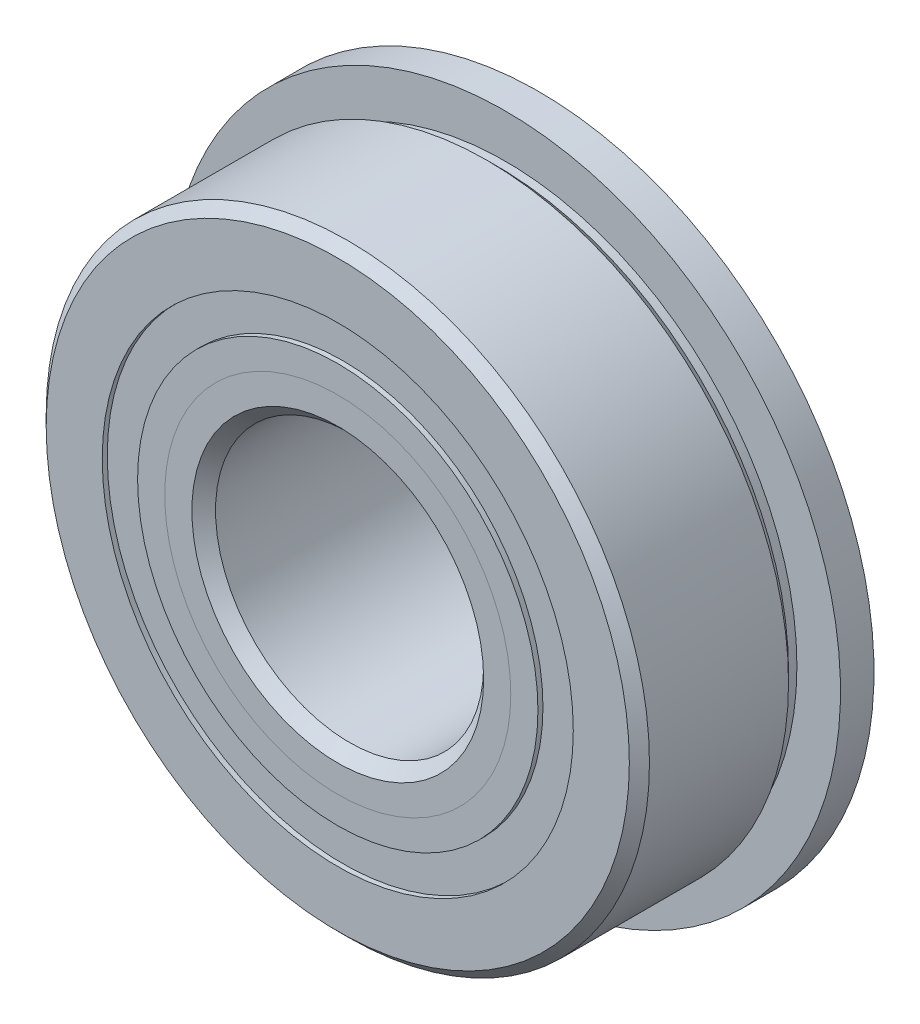
SolidWorks part; units mm, degrees
ref_plane "Front Plane" through (0, 0, 0) normal (0, 0, 1) x (1, 0, 0)
ref_plane "Top Plane" through (0, 0, 0) normal (0, 1, 0) x (1, 0, 0)
ref_plane "Right Plane" through (0, 0, 0) normal (1, 0, 0) x (0, 0, -1)
sketch "Sketch1" plane through (0, 0, 0) normal (1, 0, 0) x (0, 0, -1)
  line L0 (-4.7625, 0) -> (4.7625, 0) construction
  line L1 (0, 14.2875) -> (0, -14.2875) construction
  line L2 (4.2863, 14.2875) -> (-4.2863, 14.2875)
  line L3 (-4.2863, 14.2875) -> (-4.7625, 13.8113)
  line L4 (-4.7625, 13.8113) -> (-4.7625, 11.1561)
  line L5 (-4.7625, 11.1561) -> (-2.7214, 11.1561)
  line L6 (4.7625, 11.1561) -> (2.7214, 11.1561)
  line L7 (4.7625, 13.8113) -> (4.7625, 11.1561)
  line L8 (4.2863, 14.2875) -> (4.7625, 13.8113)
  line L9 (0, 14.2875) -> (0, 10.3187) construction
  line L10 (0, 10.3187) -> (0, 6.35) construction
  line L11 (4.7625, 0) -> (6.35, 0) construction
  arc A0 (-2.7214, 11.1561) -> (2.7214, 11.1561) centre (0, 10.3187) cw
  point P14 (0, 6.35)
  dimension "OD" = 28.575
  dimension "D1" = 45
  dimension "D2" = 0.4763
  dimension "Shaft Dia" = 12.7
  dimension "D3" = 5.4429
  dimension "D4" = 0.8374
  dimension "Width" = 9.525
  dimension "Total Wd" = 11.1125
revolve "Revolve1" add sketch "Sketch1" angle 360 about L0
sketch "Sketch2" plane through (0, 0, 0) normal (1, 0, 0) x (0, 0, -1)
  line L0 (-4.7625, 9.4814) -> (-2.7214, 9.4814)
  line L1 (-4.7625, 13.8113) -> (-4.7625, -13.8113) construction
  line L2 (-4.7625, 9.4814) -> (-4.7625, 8.196)
  line L3 (-4.7625, 8.196) -> (-3.4772, 6.9107)
  line L4 (-3.4772, 6.9107) -> (0, 6.9107)
  line L5 (0, 14.2875) -> (0, -14.2875) construction
  line L6 (0, 6.9107) -> (0, 7.4714)
  line L7 (0, 7.4714) -> (0, 6.35) construction
  line L8 (-4.7625, 9.4814) -> (-4.7625, 6.9107) construction
  line L9 (-4.7625, 6.9107) -> (-3.4772, 6.9107) construction
  arc A0 (-2.7214, 9.4814) -> (0, 7.4714) centre (0, 10.3187) ccw
  arc A1 (2.7214, 11.1561) -> (-2.7214, 11.1561) centre (0, 10.3187) ccw construction
  circle A2 centre (0, 10.3187) radius 2.8473 construction
  dimension "D1" = 45
revolve "Revolve2" add sketch "Sketch2" angle 360 about L0
sketch "Sketch3" plane through (0, 0, 0) normal (1, 0, 0) x (0, 0, -1)
  line L0 (-4.7625, 8.196) -> (-3.4772, 6.9107)
  line L1 (-3.4772, 6.9107) -> (0, 6.9107)
  line L2 (0, 6.9107) -> (0, 7.4714)
  line L3 (-4.7625, 8.196) -> (-4.7625, 6.9107)
  line L4 (-4.7625, 9.4814) -> (-4.7625, 6.9107) construction
  line L5 (-4.7625, 6.9107) -> (-4.2018, 6.35)
  line L6 (-4.2018, 6.35) -> (5.8738, 6.35)
  line L7 (10.4392, 0) -> (-10.4392, 0) construction
  line L8 (5.8738, 6.35) -> (6.35, 6.8262)
  line L10 (6.35, 6.8262) -> (6.35, 8.7376)
  line L11 (6.35, 8.7376) -> (2.368, 8.7376)
  line L13 (4.2863, 14.2875) -> (4.7625, 13.8113) construction
  circle A0 centre (0, 10.3187) radius 2.8473 construction
  arc A1 (2.368, 8.7376) -> (0, 7.4714) centre (0, 10.3187) cw
  point P18 (0, 0)
  dimension "Inner Ring OD" = 17.4752
revolve "Revolve3" add sketch "Sketch3" angle 360 about L0
sketch "Sketch5" plane through (0, 0, 0) normal (1, 0, 0) x (0, 0, -1)
  line L0 (4.7625, 13.8113) -> (4.7625, 11.1561) construction
  line L1 (4.7625, 12.4837) -> (3.175, 12.4837)
  line L2 (4.7625, 12.4837) -> (4.7625, 15.875)
  line L3 (4.7625, 15.875) -> (3.175, 15.875)
  line L4 (3.175, 12.4837) -> (3.175, 15.875)
  line L5 (6.35, 0) -> (-4.7625, 0) construction
  dimension "D1" = 1.5875
  dimension "Flange OD" = 31.75
revolve "Revolve5" add sketch "Sketch5" angle 360 about L5
sketch "Sketch6" plane through (0, 0, 0) normal (1, 0, 0) x (0, 0, -1)
  line L0 (2.3019, 14.2875) -> (2.7781, 13.8113)
  line L1 (4.2863, 14.2875) -> (-4.2863, 14.2875) construction
  line L2 (2.7781, 13.8113) -> (3.175, 13.8113)
  line L3 (3.175, 13.8113) -> (3.175, 14.2875)
  line L4 (3.175, 14.2875) -> (2.3019, 14.2875)
  line L5 (4.2863, 14.2875) -> (4.7625, 13.8113) construction
  line L6 (3.175, 12.4837) -> (3.175, 15.875) construction
  dimension "D1" = 0.3969
revolve "Cut-Revolve1" cut sketch "Sketch6" angle 360 about L0
sketch "Sketch4" plane through (0, 0, 0) normal (1, 0, 0) x (0, 0, -1)
  line L0 (-2.8473, 10.3187) -> (2.8473, 10.3187)
  circle A1 centre (0, 10.3187) radius 2.8473 construction
  arc A2 (-2.8473, 10.3187) -> (2.8473, 10.3187) centre (0, 10.3187) cw
  arc A3 (2.7214, 11.1561) -> (-2.7214, 11.1561) centre (0, 10.3187) ccw construction
revolve "Revolve4" add sketch "Sketch4" angle 360 about L0
ref_axis "Axis1" through (0, 0, -4.7625) along (0, 0, 1)
pattern_circular "CirPattern1" count 12 every 30 about axis through (0, 0, -4.7625) along (0, 0, 1) of bodies 104
sketch "Sketch7" plane through (0, 0, 0) normal (1, 0, 0) x (0, 0, -1)
  line L0 (-4.7625, 11.1561) -> (-2.7214, 11.1561) construction
  line L1 (-4.5244, 11.1561) -> (-2.8473, 11.1561)
  line L2 (-4.5244, 11.1561) -> (-4.5244, 9.4814)
  line L3 (-4.5244, 9.4814) -> (-2.8473, 9.4814)
  line L4 (-2.8473, 11.1561) -> (-2.8473, 9.4814)
  line L5 (-4.7625, 9.4814) -> (-2.7214, 9.4814) construction
  line L6 (-4.2863, 14.2875) -> (-4.7625, 13.8113) construction
  line L7 (4.7625, 11.1561) -> (2.7214, 11.1561) construction
  line L8 (4.5244, 11.1561) -> (2.8473, 11.1561)
  line L9 (4.5244, 11.1561) -> (4.5244, 8.7376)
  line L10 (4.5244, 8.7376) -> (2.8473, 8.7376)
  line L11 (2.8473, 11.1561) -> (2.8473, 8.7376)
  line L12 (6.35, 8.7376) -> (2.368, 8.7376) construction
  line L13 (4.2863, 14.2875) -> (4.7625, 13.8113) construction
  circle A0 centre (0, 10.3187) radius 2.8473 construction
  point P10 (-4.5244, 14.0494)
  point P21 (4.5244, 14.0494)
revolve "Revolve6" add sketch "Sketch7" angle 360 about L0
equation "\"D2@Sketch1\" = \"Width@Sketch1\"*.05"
equation "\"D3@Sketch1\"=\"Width@Sketch1\"/1.75"
equation "\"D4@Sketch1\" = (((\"OD@Sketch1\"-\"Width@Sketch1\")/2)/3.25)/3.5"
equation "\"D2@CirPattern1\" = 360/\"Balls@CirPattern1\""
